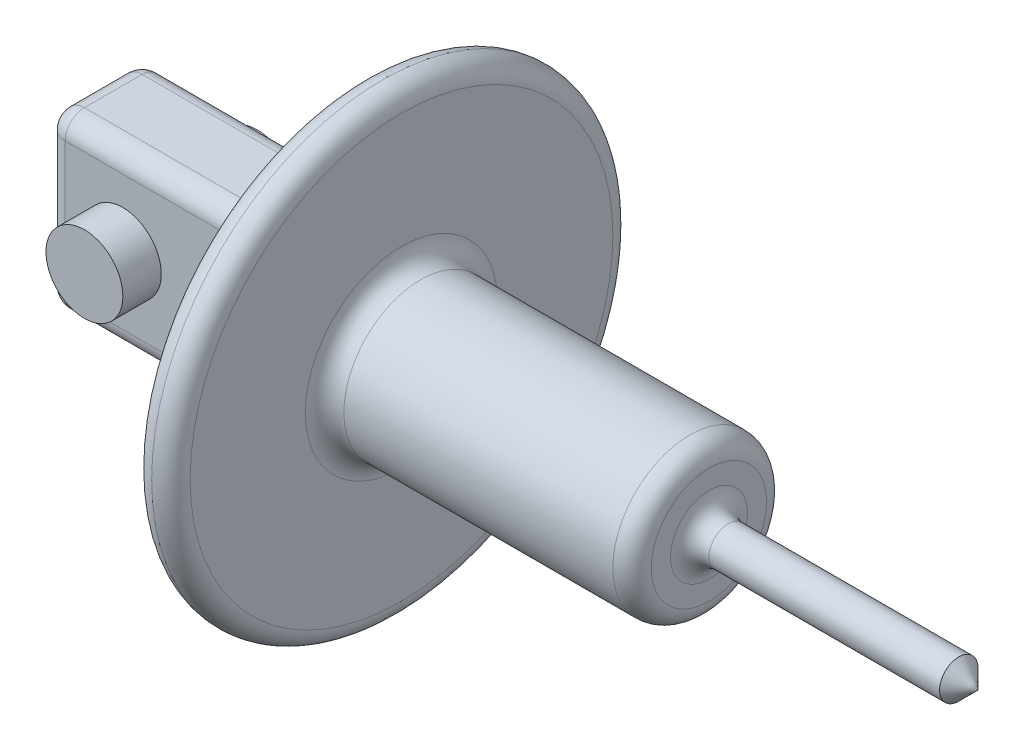
SolidWorks part; units mm, degrees
ref_plane "Front Plane" through (0, 0, 0) normal (0, 0, 1) x (1, 0, 0)
ref_plane "Top Plane" through (0, 0, 0) normal (0, 1, 0) x (1, 0, 0)
ref_plane "Right Plane" through (0, 0, 0) normal (1, 0, 0) x (0, 0, -1)
sketch "Sketch1" plane through (0, 0, 0) normal (1, 0, 0) x (0, 0, -1)
  line L1 (-12.5, 22.5) -> (12.5, 22.5)
  line L2 (-12.5, 22.5) -> (-12.5, -22.5)
  line L3 (-12.5, -22.5) -> (12.5, -22.5)
  line L4 (12.5, 22.5) -> (12.5, -22.5)
  line L5 (-12.5, 22.5) -> (12.5, -22.5) construction
  line L6 (-12.5, -22.5) -> (12.5, 22.5) construction
  circle A0 centre (0, 0) radius 60
  circle A1 centre (0, 0) radius 20
  circle A2 centre (0, 0) radius 5
  dimension "D1" = 120
  dimension "D2" = 40
  dimension "D3" = 10
  dimension "D4" = 25
  dimension "D5" = 45
extrude "Boss-Extrude1" add sketch "Sketch1" along normal blind 10 contours A0 A1 L2 L1 L4 L3 | L2 A1 | L4 A1 region at (0, 0, 15.5541) region at (0, 0, -15.5541) region at (0, 0, 58.3029)
extrude "Boss-Extrude2" add sketch "Sketch1<3>" against normal blind 80 contours A1
sketch "Sketch1<3>" plane through (0, 0, 0) normal (1, 0, 0) x (0, 0, -1) same geometry as "Sketch1"
extrude "Boss-Extrude3" add sketch "Sketch1<4>" against normal blind 70 from surface contours A2 starting at face at (-80, 0, -20)
sketch "Sketch1<4>" plane through (0, 0, 0) normal (1, 0, 0) x (0, 0, -1) same geometry as "Sketch1"
chamfer "Chamfer1" distance 5 angle 45 1 edges at (-150, 0, -5)
extrude "Boss-Extrude4" add sketch "Sketch1<5>" along normal blind 80 contours L3 L4 L1 L2
sketch "Sketch1<5>" plane through (0, 0, 0) normal (1, 0, 0) x (0, 0, -1) same geometry as "Sketch1"
sketch "Sketch3" plane through (0, 0, -12.5) normal (0, 0, -1) x (-1, 0, 0)
  line L0 (-80, 22.5) -> (-80, -22.5) construction
  line L1 (-80, 22.5) -> (-10, 22.5) construction
  circle A0 centre (-60, 0) radius 10
  dimension "D1" = 20
  dimension "D2" = 20
  dimension "D3" = 22.5
extrude "Boss-Extrude5" add sketch "Sketch3" along normal blind 10
mirror "Mirror1" about plane through (0, 0, 0) normal (0, 0, 1) of "Boss-Extrude5"
fillet "Fillet1" radius 5 17 edges at (10, 0, -12.5) (10, 22.5, 0) (10, -22.5, 0) (0, 0, -20) (-80, 0, -5) (-80, 0, -20) (10, 0, -60) (0, 0, -60) (10, 0, 12.5) (45, -22.5, -12.5) (45, -22.5, 12.5) (80, -22.5, 0) (80, 0, -12.5) (80, 0, 12.5) (45, 22.5, -12.5) (80, 22.5, 0) (45, 22.5, 12.5)
sketch "Sketch5" plane through (0, 0, 0) normal (0, 0, 1) x (1, 0, 0)
  point P0 (60, 0)
sketch "Sketch6" plane through (0, 0, 0) normal (0, 1, 0) x (1, 0, 0)
  point P0 (-150, 0)
  point P1 (-130.9994, -45.9569)
move or copy body "Body-Move/Copy1" bodies to move or copy 106 copy no translate (150, 0, 0)
move or copy body "Body-Move/Copy4" bodies to move or copy 107 copy no rotation origin (0, 0, 0) rotation axis (0, 1, 0) rotation angle 180
sketch "Sketch7" plane through (0, 0, 0) normal (0, 0, 1) x (1, 0, 0)
  point P0 (-210, 0)
move or copy body "Body-Move/Copy5" bodies to move or copy 110 copy no translate (210, 0, 0)
